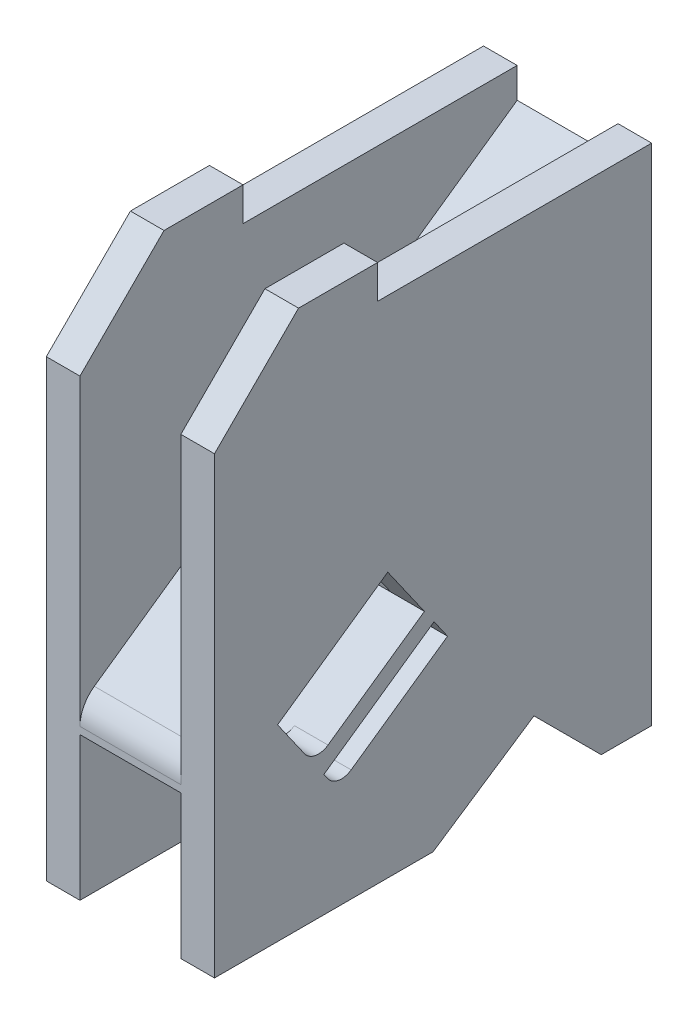
SolidWorks part; units mm, degrees
ref_plane "Front Plane" through (0, 0, 0) normal (0, 0, 1) x (1, 0, 0)
ref_plane "Top Plane" through (0, 0, 0) normal (0, 1, 0) x (1, 0, 0)
ref_plane "Right Plane" through (0, 0, 0) normal (1, 0, 0) x (0, 0, -1)
sketch "Sketch5" plane through (0, 0, 0) normal (0, 1, 0) x (1, 0, 0)
  line L1 (0, 0) -> (50, 0)
  line L2 (0, 0) -> (0, 130)
  line L3 (0, 130) -> (50, 130)
  line L4 (50, 0) -> (50, 130)
  dimension "D1" = 130
  dimension "D2" = 50
extrude "Boss-Extrude1" add sketch "Sketch5" along normal blind 150
sketch "Sketch7" plane through (50, 0, 0) normal (1, 0, 0) x (0, 0, -1)
  line L0 (130, 141.027) -> (0, 50)
  line L1 (115.8456, 131.116) -> (0, 50) construction
  line L2 (0, 150) -> (0, 0) construction
  line L3 (130, 133.7023) -> (0, 42.6754)
  line L4 (119.2871, 126.201) -> (3.4415, 45.0851) construction
  line L5 (130, 150) -> (130, 0) construction
  line L7 (0, 0) -> (130, 0)
  line L8 (130, 0) -> (130, 150)
  line L9 (130, 150) -> (0, 150)
  line L10 (0, 150) -> (0, 0)
  line L11 (0, 0) -> (130, 0)
  line L12 (130, 0) -> (130, 150)
  line L13 (130, 150) -> (0, 150)
  line L14 (0, 150) -> (0, 0)
  point P3 (0, 0)
  point P14 (0, 0)
  point P17 (0, 0)
  line M6 (0, 0) -> (130, 0)
  line M7 (130, 0) -> (130, 150)
  line M8 (130, 150) -> (0, 150)
  line M9 (0, 150) -> (0, 0)
  dimension "D1" = 50
  dimension "D2" = 55
  dimension "D3" = 0
  dimension "D4" = 6
extrude "Cut-Extrude1" cut sketch "Sketch7" against normal mid plane 30 from offset 25 contours L3 M7 M9 M6 | L0 M7 M8 M9 region at (50, 116.4204, -46.9015) region at (50, 48.0093, -76.182) offset against normal yes
ref_plane "Plane2" through (25, 0, 0) normal (-1, 0, 0) x (0, 0, 1)
sketch "Sketch17" plane through (0, 275.4121, -321.9218) normal (0, -0.8192, -0.5736) x (1, 0, 0)
  line L0 (40, 315.183) -> (40, 238.4945) construction
  line L1 (10, 374.2932) -> (40, 374.2932)
  line L2 (10, 374.2932) -> (10, 334.2932)
  line L3 (10, 334.2932) -> (40, 334.2932)
  line L4 (40, 374.2932) -> (40, 334.2932)
  line L6 (10, 315.183) -> (10, 238.4945) construction
  line L8 (10, 234.2932) -> (10, 392.9939) construction
  line L9 (10, 234.2932) -> (40, 234.2932) construction
  point P4 (0, 0)
  point P8 (37.5, 101.061)
  point P9 (37.5, 68.2031)
  point P14 (10, 340.9575)
  dimension "D1" = 40
  dimension "D2" = 100
extrude "Boss-Extrude3" add sketch "Sketch17" against normal blind 5 from offset 30
sketch "Sketch10" plane through (0, 33.5505, 23.4923) normal (0, 0.8192, 0.5736) x (1, 0, 0)
  line L0 (25, 28.6788) -> (25, 172.6872) construction
  line L1 (10, 28.6788) -> (40, 28.6788) construction
  line L2 (50, 86.0365) -> (50, 0) construction
  line L3 (0, 83.1783) -> (50, 83.1783)
  line L4 (0, 83.1783) -> (0, 53.1783)
  line L5 (0, 53.1783) -> (50, 53.1783)
  line L6 (50, 83.1783) -> (50, 53.1783)
  line L7 (0, 83.1783) -> (50, 53.1783) construction
  line L8 (0, 53.1783) -> (50, 83.1783) construction
  line L9 (10, 183.1783) -> (40, 183.1783) construction
  circle A0 centre (25, 68.1783) radius 8.75
  point P4 (25, 68.1783)
  point P9 (0, 0)
  dimension "D1" = 17.5
  dimension "D2" = 30
  dimension "D3" = 100
extrude "Cut-Extrude3" cut sketch "Sketch10" against normal blind 100 contours A0 region at (25, 72.656, -32.3561)
sketch "Sketch18" plane through (0, 0, 0) normal (1, 0, 0) x (0, 0, -1)
  line L0 (130, 150) -> (130, 0) construction
  line L1 (0, 150) -> (48.5, 150)
  line L2 (0, 150) -> (0, 160)
  line L3 (0, 160) -> (48.5, 160)
  line L4 (48.5, 150) -> (48.5, 160)
  dimension "D1" = 81.5
  dimension "D2" = 10
extrude "Boss-Extrude4" add sketch "Sketch18" along normal blind 10
extrude "Boss-Extrude5" add sketch "Sketch18<2>" along normal blind 10 from offset 40
sketch "Sketch18<2>" plane through (0, 0, 0) normal (1, 0, 0) x (0, 0, -1) same geometry as "Sketch18"
chamfer "Chamfer1" distance 25 angle 45 2 edges at (5, 160, 0) (45, 160, 0)
sketch "Sketch21" plane through (0, 0, 0) normal (1, 0, 0) x (0, 0, -1)
  line L0 (62.4242, 63.1905) -> (29.6581, 40.2475)
  line L1 (62.4242, 63.1905) -> (51.5263, 78.7544)
  line L2 (29.6581, 40.2475) -> (18.7602, 55.8114)
  line L3 (51.5263, 78.7544) -> (18.7602, 55.8114)
  line L4 (130, 133.7023) -> (0, 42.6754) construction
  line L5 (65.2921, 59.0948) -> (32.526, 36.1517)
  line L6 (65.2921, 59.0948) -> (32.526, 36.1517)
  line L7 (65.2921, 59.0948) -> (69.3071, 53.3607)
  line L8 (32.526, 36.1517) -> (36.541, 30.4177)
  line L9 (69.3071, 53.3607) -> (36.541, 30.4177)
  dimension "D1" = 90
  dimension "D3" = 7
  dimension "D2" = 5
extrude "Cut-Extrude5" cut sketch "Sketch21" along normal blind 70 contours L1 L3 L2 L0 | L9 L7 L5 L8 region at (0, 59.501, -40.5922) region at (0, 44.7562, -50.9166)
fillet "Fillet1" radius 5 4 edges at (5, 30.4177, -36.541) (45, 30.4177, -36.541) (5, 40.2475, -29.6581) (45, 40.2475, -29.6581)
sketch "Sketch22" plane through (0, 0, 0) normal (-1, 0, 0) x (0, 0, 1)
  line L0 (-115, 0) -> (-95, 20)
  line L1 (-130, 0) -> (0, 0) construction
  line L3 (-95, 20) -> (-65, 0)
  line L4 (-115, 0) -> (-65, 0)
  dimension "D1" = 20
  dimension "D2" = 20
  dimension "D3" = 15
  dimension "D4" = 65
extrude "Cut-Extrude6" cut sketch "Sketch22" against normal blind 70
fillet "Fillet2" radius 10 1 edges at (25, 50, 0)
